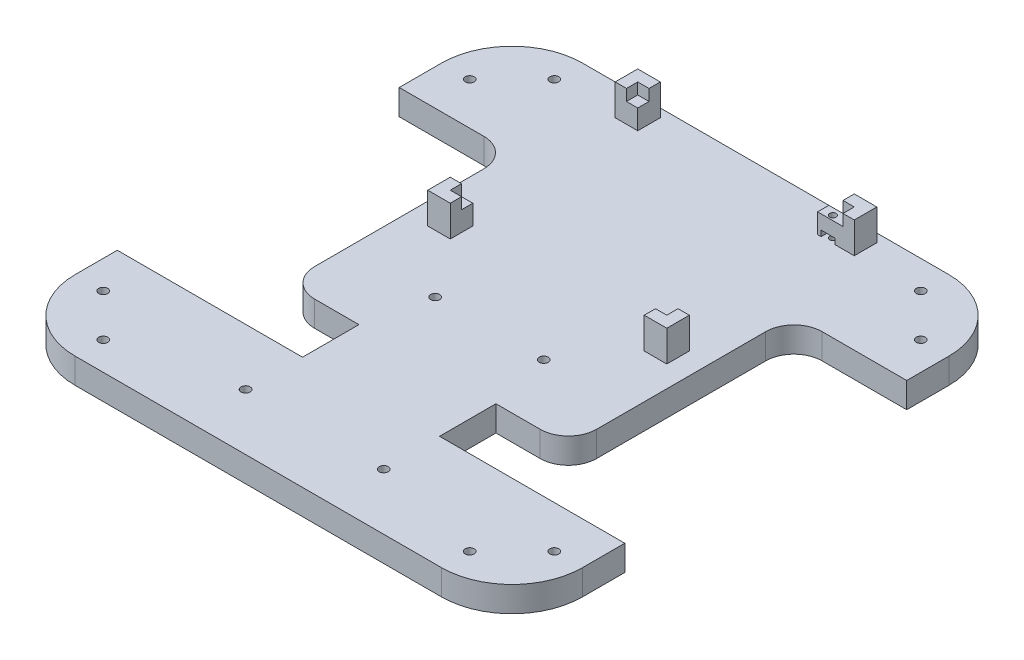
SolidWorks part; units mm, degrees
ref_plane "Front Plane" through (0, 0, 0) normal (0, 0, 1) x (1, 0, 0)
ref_plane "Top Plane" through (0, 0, 0) normal (0, 1, 0) x (1, 0, 0)
ref_plane "Right Plane" through (0, 0, 0) normal (1, 0, 0) x (0, 0, -1)
sketch "Sketch1" plane through (0, 0, 0) normal (0, 1, 0) x (1, 0, 0)
  line L1 (-65, -90) -> (65, -90)
  line L2 (-90, -65) -> (-90, 65)
  line L3 (-65, 90) -> (65, 90)
  line L4 (90, -65) -> (90, 65)
  arc A0 (-90, 65) -> (-65, 90) centre (-65, 65) cw
  arc A1 (65, 90) -> (90, 65) centre (65, 65) cw
  arc A2 (90, -65) -> (65, -90) centre (65, -65) cw
  arc A3 (-65, -90) -> (-90, -65) centre (-65, -65) cw
  point P4 (-90, 0)
  point P6 (0, 90)
  dimension "D3" = 25
  dimension "D1" = 180
  dimension "D2" = 180
extrude "Plate" add sketch "Sketch1" along normal blind 9
sketch "Sketch3" plane through (0, 9, 0) normal (0, 1, 0) x (1, 0, 0)
  line L0 (-65, 90) -> (-65, -90) construction
  line L1 (65, 90) -> (65, -90) construction
  line L2 (-90, 65) -> (90, 65) construction
  line L3 (-90, -65) -> (90, -65) construction
  circle A0 centre (-65, 80) radius 1.6
  circle A1 centre (-80, 65) radius 1.6
  circle A2 centre (80, 65) radius 1.6
  circle A3 centre (80, -65) radius 1.6
  circle A4 centre (65, 80) radius 1.6
  circle A5 centre (65, -80) radius 1.6
  circle A6 centre (-65, -80) radius 1.6
  circle A7 centre (-80, -65) radius 1.6
  dimension "D1" = 3.2
  dimension "D2" = 15
  dimension "D3" = 15
  dimension "D4" = 15
  dimension "D5" = 15
  dimension "D6" = 15
  dimension "D7" = 15
  dimension "D8" = 15
  dimension "D9" = 15
extrude "Hex Holes" cut sketch "Sketch3" against normal through all
sketch "Sketch4" plane through (0, 9, 0) normal (0, 1, 0) x (1, 0, 0)
  line L0 (-90, -65) -> (-90, 65) construction
  line L1 (-65, -90) -> (65, -90) construction
  circle A0 centre (-24.5, -70) radius 1.6
  circle A1 centre (24.5, -70) radius 1.6
  circle A2 centre (-19.25, -8) radius 1.6
  circle A3 centre (19.25, -8) radius 1.6
  dimension "D1" = 3.2
  dimension "D2" = 62
  dimension "D3" = 49
  dimension "D4" = 5.25
  dimension "D5" = 38.5
  dimension "D6" = 65.5
  dimension "D7" = 20
extrude "Arduino Holes" cut sketch "Sketch4" against normal through all
sketch "Sketch5" plane through (0, 9, 0) normal (0, 1, 0) x (1, 0, 0)
  line L0 (-90, -65) -> (-90, 65) construction
  line L1 (-90, -50) -> (-50, -50)
  line L2 (-90, -50) -> (-90, 50)
  line L3 (-90, 50) -> (-50, 50)
  line L4 (-50, -50) -> (-50, 50)
  line L5 (90, -65) -> (90, 65) construction
  line L6 (90, -50) -> (50, -50)
  line L7 (90, -50) -> (90, 50)
  line L8 (90, 50) -> (50, 50)
  line L9 (50, -50) -> (50, 50)
  line L10 (-90, 0) -> (90, 0) construction
  point P14 (-90, 0)
  point P15 (90, 0)
  dimension "D1" = 100
  dimension "D3" = 40
extrude "Cut-Extrude1" cut sketch "Sketch5" against normal through all
sketch "Sketch10" plane through (0, 9, 0) normal (0, 1, 0) x (1, 0, 0)
  line L0 (-65, -90) -> (65, -90) construction
  line L1 (-50, -50) -> (-50, 50) construction
  line L2 (-50, -50) -> (-24.3, -50)
  line L3 (-50, -50) -> (-50, -30)
  line L4 (-50, -30) -> (-24.3, -30)
  line L5 (-24.3, -50) -> (-24.3, -30)
  line L6 (50, -50) -> (24.3, -50)
  line L7 (50, -50) -> (50, -30)
  line L8 (50, -30) -> (24.3, -30)
  line L9 (24.3, -50) -> (24.3, -30)
  line L10 (50, 50) -> (50, -50) construction
  point P0 (0, 0)
  dimension "D1" = 48.6
  dimension "D2" = 40
  dimension "D3" = 20
extrude "Cut-Extrude4" cut sketch "Sketch10" against normal blind 10
fillet "Fillet1" radius 10 4 edges at (50, 4.5, -50) (-50, 4.5, -50) (50, 4.5, 30) (-50, 4.5, 30)
sketch "Sketch6" plane through (0, 9, 0) normal (0, 1, 0) x (1, 0, 0)
  line L0 (-65, 90) -> (65, 90) construction
  line L1 (-38.4, 16.5) -> (38.4, 16.5) construction
  line L2 (-38.4, 16.5) -> (-38.4, 83) construction
  line L3 (-38.4, 83) -> (38.4, 83) construction
  line L4 (38.4, 16.5) -> (38.4, 83) construction
  line L5 (34.4, 83) -> (38.4, 83)
  line L6 (38.4, 83) -> (38.4, 79)
  line L7 (38.4, 79) -> (42.4, 79)
  line L8 (42.4, 79) -> (42.4, 87)
  line L9 (42.4, 87) -> (34.4, 87)
  line L10 (34.4, 87) -> (34.4, 83)
  line L11 (38.4, 20.5) -> (38.4, 16.5)
  line L12 (38.4, 16.5) -> (34.4, 16.5)
  line L13 (34.4, 16.5) -> (34.4, 12.5)
  line L14 (34.4, 12.5) -> (42.4, 12.5)
  line L15 (42.4, 12.5) -> (42.4, 20.5)
  line L16 (42.4, 20.5) -> (38.4, 20.5)
  line L17 (-38.4, 16.5) -> (-34.4, 16.5)
  line L18 (-34.4, 16.5) -> (-34.4, 12.5)
  line L19 (-34.4, 12.5) -> (-42.4, 12.5)
  line L20 (-42.4, 12.5) -> (-42.4, 20.5)
  line L21 (-42.4, 20.5) -> (-38.4, 20.5)
  line L22 (-38.4, 20.5) -> (-38.4, 16.5)
  line L23 (-38.4, 83) -> (-34.4, 83)
  line L24 (-34.4, 83) -> (-34.4, 87)
  line L25 (-34.4, 87) -> (-42.4, 87)
  line L26 (-42.4, 87) -> (-42.4, 79)
  line L27 (-42.4, 79) -> (-38.4, 79)
  line L28 (-38.4, 79) -> (-38.4, 83)
  point P6 (0, 90)
  point P7 (0, 83)
  dimension "D1" = 66.5
  dimension "D2" = 76.8
  dimension "D3" = 7
  dimension "D4" = 4
extrude "Boss-Extrude1" add sketch "Sketch6" along normal blind 11
sketch "Sketch7" plane through (0, 9, 0) normal (0, 1, 0) x (1, 0, 0)
  line L1 (-38.4, 16.5) -> (-34.4, 16.5)
  line L2 (-38.4, 16.5) -> (-38.4, 20.5)
  line L3 (-38.4, 20.5) -> (-34.4, 20.5)
  line L4 (-34.4, 16.5) -> (-34.4, 20.5)
  line L5 (38.4, 16.5) -> (34.4, 16.5)
  line L6 (38.4, 16.5) -> (38.4, 20.5)
  line L7 (38.4, 20.5) -> (34.4, 20.5)
  line L8 (34.4, 16.5) -> (34.4, 20.5)
  line L9 (-38.4, 83) -> (-34.4, 83)
  line L10 (-38.4, 83) -> (-38.4, 79)
  line L11 (-38.4, 79) -> (-34.4, 79)
  line L12 (-34.4, 83) -> (-34.4, 79)
  line L13 (38.4, 83) -> (29.4, 83)
  line L14 (38.4, 83) -> (38.4, 79)
  line L15 (38.4, 79) -> (29.4, 79)
  line L16 (29.4, 83) -> (29.4, 79)
  dimension "D1" = 4
  dimension "D2" = 4
  dimension "D3" = 9
extrude "Boss-Extrude2" add sketch "Sketch7" along normal blind 7
sketch "Sketch8" plane through (0, 16, 0) normal (0, 1, 0) x (1, 0, 0)
  line L0 (38.4, 83) -> (34.4, 83) construction
  line L1 (38.4, 79) -> (38.4, 83) construction
  circle A0 centre (33.15, 80.65) radius 1.15
  dimension "D1" = 2.3
  dimension "D2" = 2.35
  dimension "D3" = 5.25
extrude "Cut-Extrude2" cut sketch "Sketch8" against normal through all
sketch "Sketch9" plane through (0, 0, -79) normal (0, 0, 1) x (1, 0, 0)
  line L0 (29.4, 9) -> (42.4, 9) construction
  line L1 (30.65, 11) -> (35.65, 11)
  line L2 (30.65, 11) -> (30.65, 9)
  line L3 (30.65, 9) -> (35.65, 9)
  line L4 (35.65, 11) -> (35.65, 9)
  line L6 (29.4, 16) -> (29.4, 9) construction
  point P6 (33.15, 11)
  dimension "D1" = 5
  dimension "D2" = 2
  dimension "D3" = 3.75
extrude "Cut-Extrude3" cut sketch "Sketch9" against normal through all
